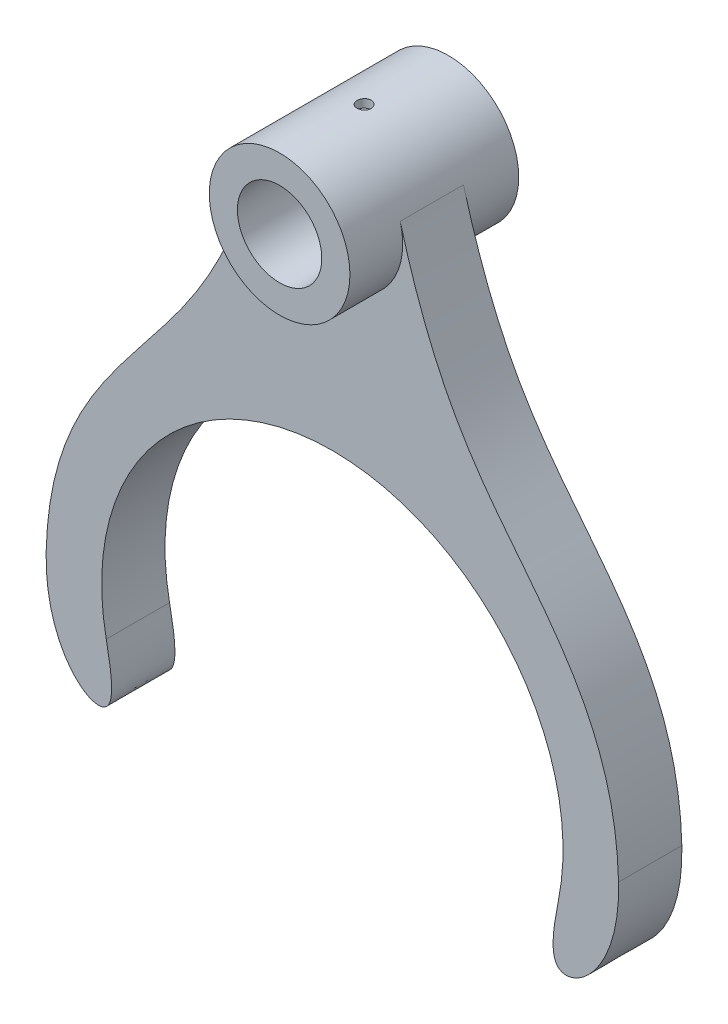
SolidWorks part; units mm, degrees
ref_plane "Front Plane" through (0, 0, 0) normal (0, 0, 1) x (1, 0, 0)
ref_plane "Top Plane" through (0, 0, 0) normal (0, 1, 0) x (1, 0, 0)
ref_plane "Right Plane" through (0, 0, 0) normal (1, 0, 0) x (0, 0, -1)
sketch "Sketch1" plane through (0, 0, 0) normal (0, 0, 1) x (1, 0, 0)
  line L1 (0, 0) -> (0, 200.3122) construction
  arc A0 (80.3693, -16.2717) -> (-80.3693, -16.2717) centre (0, 0) ccw
  circle A2 centre (0, 158) radius 25
  circle A3 centre (0, 158) radius 15
  spline S0 degree 3 poles (-101.7377, 0) (-100.6203, 43.9384) (-64.3464, 80.3125) (-34.6334, 126.2249) (-24.1104, 164.6098) knots 0 0 0 0 0.598566 1 1 1 1
  spline S1 degree 3 poles (101.7377, 0) (100.6203, 43.9384) (64.3464, 80.3125) (34.6334, 126.2249) (24.1104, 164.6098) knots 0 0 0 0 0.598566 1 1 1 1
  spline S2 degree 3 poles (-101.7377, 0) (-102.4981, -29.8999) (-76.5062, -48.3224) (-78.1986, -26.9933) (-80.3693, -16.2717) knots 0 0 0 0 0.67656 1 1 1 1
  spline S3 degree 3 poles (101.7377, 0) (102.4981, -29.8999) (76.5062, -48.3224) (78.1986, -26.9933) (80.3693, -16.2717) knots 0 0 0 0 0.67656 1 1 1 1
  point P1 (-36.3279, 133.3278)
  point P9 (-60.07, 95.2154)
  point P12 (0, 0)
  point P16 (-40.5758, 118.8292)
  point P21 (-59.5463, 90.9004)
  dimension "D1" = 164
  dimension "D2" = 50
  dimension "D3" = 30
  dimension "D4" = 158
extrude "Boss-Extrude1" add sketch "Sketch1" along normal mid plane 22.5 contours A0 L1 A2 S0 S2 | L1 A0 S3 S1 A2 region at (-51.0434, 69.8375, 0) region at (51.0434, 69.8357, 0)
extrude "Boss-Extrude2" add sketch "Sketch1<3>" along normal mid plane 60 contours A2 L1 A3 | L1 A2 A3 region at (-19.4332, 143.1773, 0) region at (0.559, 138, 0)
sketch "Sketch1<3>" plane through (0, 0, 0) normal (0, 0, 1) x (1, 0, 0) same geometry as "Sketch1"
ref_plane "Plane1" through (0, 180, 0) normal (0, 1, 0) x (1, 0, 0)
sketch "Sketch3" plane through (0, 180, 0) normal (0, 1, 0) x (1, 0, 0)
  circle A0 centre (0, 0) radius 2.5
  dimension "D1" = 5
extrude "Cut-Extrude1" cut sketch "Sketch3" along normal through all
